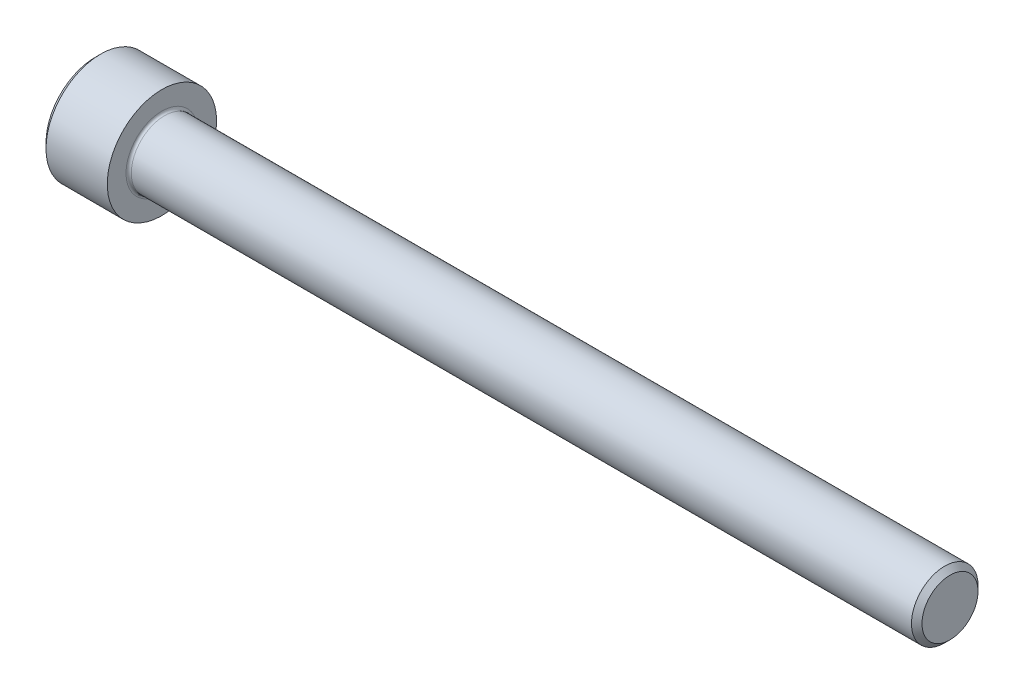
SolidWorks part; units mm, degrees
material "Alloy Steel"
ref_plane "Z Plane" through (0, 0, 0) normal (0, 0, 1) x (1, 0, 0)
ref_plane "Y Plane" through (0, 0, 0) normal (0, 1, 0) x (1, 0, 0)
ref_plane "X Plane" through (0, 0, 0) normal (1, 0, 0) x (0, 0, -1)
sketch "Sketch1" plane through (0, 0, 0) normal (0, 1, 0) x (1, 0, 0)
  line L0 (0, 3.9624) -> (0, -3.9624) construction
  line L1 (0, 0) -> (0, 3.9624)
  line L2 (0, 3.9624) -> (4.826, 3.9624)
  line L3 (4.826, 3.9624) -> (4.826, 2.413)
  line L4 (4.826, 2.413) -> (61.976, 2.413)
  line L5 (61.976, 2.413) -> (61.976, -2.413) construction
  line L6 (61.976, 2.413) -> (61.976, 0)
  line L7 (61.976, 0) -> (0, 0)
  line L8 (0, -3.9624) -> (1.6087, -3.9624) construction
  line L9 (1.6087, -3.9624) -> (3.2173, -3.9624) construction
  line L10 (3.2173, -3.9624) -> (4.826, -3.9624) construction
  point P2 (0, 0)
  point P5 (61.976, 0)
  dimension "Head Diameter" = 7.9248
  dimension "Thread Diameter" = 4.826
  dimension "Thread Length" = 57.15
revolve "Body" add sketch "Sketch1" angle 360 about L7
ref_plane "Plane1" through (3.2173, 0, 0) normal (1, 0, 0) x (0, 0, -1)
sketch "Sketch2" plane through (0, 0, 0) normal (-1, 0, 0) x (0, 0, 1)
  line L1 (-2.2914, 0) -> (-1.1457, -1.9844)
  line L2 (-1.1457, -1.9844) -> (1.1457, -1.9844)
  line L3 (1.1457, -1.9844) -> (2.2914, 0)
  line L4 (2.2914, 0) -> (1.1457, 1.9844)
  line L5 (1.1457, 1.9844) -> (-1.1457, 1.9844)
  line L6 (-1.1457, 1.9844) -> (-2.2914, 0)
  circle A0 centre (0, 0) radius 1.9844 construction
  dimension "Hex Head" = 3.9688
extrude "Hex" cut sketch "Sketch2" against normal up to surface (3.2173 mm away) up to plane "Plane1"
chamfer "Chamfer1" distance 0.381 angle 45 2 edges at (61.976, 0, -2.413) (0, 0, -3.9624)
fillet "Fillet1" radius 0.1905 1 edges at (4.826, 0, -2.413)
sketch "Sketch3" plane through (0, 0, 0) normal (1, 0, 0) x (0, 0, -1)
  circle A0 centre (0, 0) radius 2.2914
extrude "Hex Chamfer" cut sketch "Sketch3" along normal blind 2.54 draft 45
